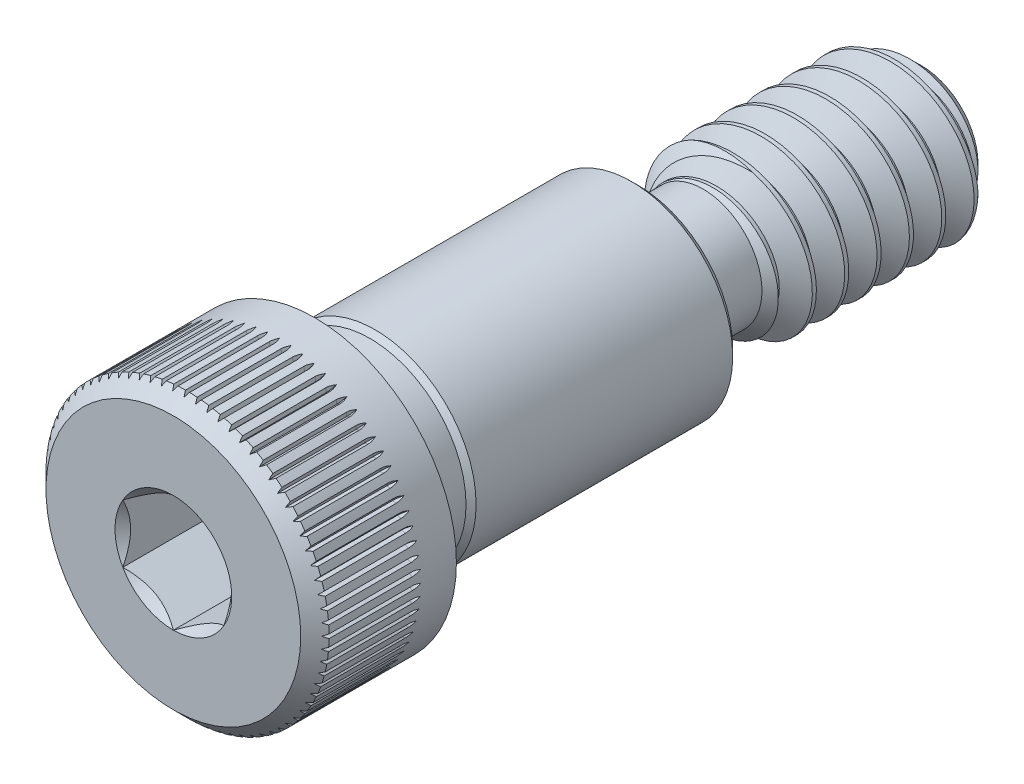
SolidWorks part; units mm, degrees
ref_plane "Front Plane" through (0, 0, 0) normal (0, 0, 1) x (1, 0, 0)
ref_plane "Top Plane" through (0, 0, 0) normal (0, 1, 0) x (1, 0, 0)
ref_plane "Right Plane" through (0, 0, 0) normal (1, 0, 0) x (0, 0, -1)
sketch "Sketch2" plane through (0, 0, 0) normal (1, 0, 0) x (0, 0, -1)
  line L0 (-14.6844, 0) -> (14.6844, 0) construction
  line L1 (-14.6844, 0) -> (-14.6844, 5.5562)
  line L2 (-14.6844, 5.5562) -> (-9.1281, 5.5563)
  line L3 (-9.1281, 5.5563) -> (-9.1281, 3.9688)
  line L4 (-9.1281, 3.9688) -> (3.5719, 3.9688)
  line L5 (3.5719, 3.175) -> (14.6844, 3.175)
  line L6 (14.6844, 3.175) -> (14.6844, 0)
  line L7 (14.605, 3.3125) -> (15.24, 2.2126) construction
  line L8 (15.24, 2.2126) -> (15.875, 3.3125) construction
  line L9 (15.875, 3.3125) -> (14.605, 3.3125) construction
  line L10 (14.6844, 3.175) -> (15.7956, 3.175) construction
  line L11 (15.24, 3.3125) -> (15.24, 3.175) construction
  line L12 (15.24, 3.175) -> (15.24, 2.3501) construction
  line L13 (15.24, 2.3501) -> (15.24, 2.2126) construction
  line L14 (15.1606, 2.3501) -> (15.3194, 2.3501)
  line L15 (14.6447, 3.2437) -> (15.8353, 3.2437)
  line L16 (15.3194, 2.3501) -> (15.8353, 3.2437)
  line L17 (15.1606, 2.3501) -> (14.6447, 3.2437)
  line L18 (14.6844, 0) -> (14.6844, -3.175) construction
  line L19 (3.5719, -3.9688) -> (3.5719, 0) construction
  line L20 (3.5719, 0) -> (3.5719, 3.9688) construction
  line L21 (-14.6844, 0) -> (-14.6844, -5.5562) construction
  point P11 (-6.7659, 3.9688)
  point P12 (11.5094, -3.175)
  point P22 (15.24, 3.2437)
  point P23 (3.0162, 0)
  point P25 (-3.0162, 0)
  point P26 (-9.1281, -5.5562)
  point P29 (3.5719, -3.9688)
  dimension "Head Height" = 5.5562
  dimension "Shoulder Diameter" = 7.9375
  dimension "Screw Size Decimal Equivalent" = 6.35
  dimension "Thread Length" = 11.1125
  dimension "Head Diameter" = 11.1125
  dimension "Undercut Length" = 2.3622
  dimension "Pitch" = 1.27
  dimension "D2" = 0.1588
  dimension "D1" = 3.175
  dimension "D3" = 11.6681
  dimension "D4" = 11.6681
  dimension "Shoulder Length" = 12.7
sketch "Sketch3" plane through (0, 0, 0) normal (0, 0, 1) x (1, 0, 0)
  line L1 (0, 2.2914) -> (-1.9844, 1.1457)
  line L2 (-1.9844, 1.1457) -> (-1.9844, -1.1457)
  line L3 (-1.9844, -1.1457) -> (0, -2.2914)
  line L4 (0, -2.2914) -> (1.9844, -1.1457)
  line L5 (1.9844, -1.1457) -> (1.9844, 1.1457)
  line L6 (1.9844, 1.1457) -> (0, 2.2914)
  circle A0 centre (0, 0) radius 1.9844 construction
  dimension "Drive Size" = 3.9688
sketch "Sketch4" plane through (0, 0, 0) normal (1, 0, 0) x (0, 0, -1)
  line L0 (-9.1281, 5.5563) -> (-14.1287, 5.5562)
  line L1 (-14.1287, 5.5562) -> (-14.6844, 5.0006)
  line L2 (-9.1281, 5.5563) -> (-9.1281, 3.9688)
  line L3 (-9.1281, 3.9688) -> (-8.9297, 3.7703)
  line L4 (-8.9297, 3.7703) -> (-6.9644, 3.7703)
  line L5 (-6.9644, 3.7703) -> (-6.7659, 3.9688)
  line L6 (-9.1281, 3.9688) -> (3.5719, 3.9688) construction
  line L7 (-14.6844, 0) -> (14.6844, 0) construction
  line L8 (-6.7659, 3.9688) -> (3.3073, 3.9688)
  line L9 (3.3073, 3.9688) -> (3.5719, 3.7042)
  line L10 (3.5719, 3.7042) -> (3.5719, 0)
  line L11 (3.5719, 3.9688) -> (3.5719, 3.7042) construction
  line L12 (3.5719, 3.7042) -> (3.5719, 3.4396) construction
  line L13 (3.5719, 3.4396) -> (3.5719, 3.175) construction
  line L14 (-14.6844, 5.0006) -> (-14.6844, 0)
  line L15 (-14.6844, 5.5562) -> (-9.1281, 5.5562) construction
  line L16 (-14.6844, 0) -> (3.5719, 0)
  dimension "D1" = 45
  dimension "D2" = 7.5406
  dimension "D3" = 45
  dimension "D4" = 45
  dimension "D5" = 10.0012
revolve "Revolve1" add sketch "Sketch4" angle 360 about L16
sketch "Sketch5" plane through (0, 0, 14.6844) normal (0, 0, 1) x (1, 0, 0)
  line L0 (1.9844, 1.1457) -> (0, 2.2914) construction
  line L1 (1.9844, -1.1457) -> (1.9844, 1.1457) construction
  line L2 (0, -2.2914) -> (1.9844, -1.1457) construction
  line L3 (-1.9844, -1.1457) -> (0, -2.2914) construction
  line L4 (-1.9844, 1.1457) -> (-1.9844, -1.1457) construction
  line L5 (0, 2.2914) -> (-1.9844, 1.1457) construction
  line L6 (1.9844, 1.1457) -> (0, 2.2914)
  line L7 (1.9844, -1.1457) -> (1.9844, 1.1457)
  line L8 (0, -2.2914) -> (1.9844, -1.1457)
  line L9 (-1.9844, -1.1457) -> (0, -2.2914)
  line L10 (-1.9844, 1.1457) -> (-1.9844, -1.1457)
  line L11 (0, 2.2914) -> (-1.9844, 1.1457)
extrude "Cut-Extrude1" cut sketch "Sketch5" against normal blind 4.1672
sketch "Sketch6" plane through (0, 0, 14.6844) normal (0, 0, 1) x (1, 0, 0)
  circle A0 centre (0, 0) radius 2.2914
extrude "Cut-Extrude4" cut sketch "Sketch6" against normal blind 4.1672 draft 45
sketch "Sketch7" plane through (0, 0, 0) normal (1, 0, 0) x (0, 0, -1)
  line L0 (3.5719, 3.175) -> (13.7319, 3.175)
  line L1 (3.5719, 3.175) -> (14.6844, 3.175) construction
  line L2 (13.7319, 3.175) -> (14.6844, 2.2225)
  line L3 (14.6844, 3.175) -> (14.6844, 0) construction
  line L4 (14.6844, 2.2225) -> (14.6844, 0)
  line L5 (14.6844, 0) -> (3.5719, 0)
  line L6 (3.5719, -3.7042) -> (3.5719, 3.7042) construction
  line L7 (3.5719, 0) -> (3.5719, 3.175)
  dimension "D1" = 45
  dimension "D2" = 0.9525
revolve "Revolve2" add sketch "Sketch7" angle 360 about L5
sketch "Sketch10" plane through (0, 0, 0) normal (1, 0, 0) x (0, 0, -1)
  line L0 (4.4355, 2.3114) -> (6.1119, 2.3114)
  line L1 (6.1119, 2.3114) -> (7.7692, 3.9688)
  line L2 (7.7692, 3.9688) -> (3.5719, 3.9688)
  line L3 (3.5719, 3.9688) -> (3.5719, 3.175)
  line L4 (3.5719, -3.7042) -> (3.5719, 3.7042) construction
  line L5 (14.6844, 0) -> (3.5719, 0) construction
  line L6 (-14.6844, 0) -> (14.6844, 0) construction
  arc A0 (3.5719, 3.175) -> (4.4355, 2.3114) centre (4.4355, 3.175) ccw
  dimension "Flat OD" = 4.6228
  dimension "Flat" = 2.54
  dimension "D3" = 45
revolve "Cut-Revolve1" cut sketch "Sketch10" angle 360 about L5
sketch "Sketch8" plane through (0, 0, -14.6844) normal (0, 0, -1) x (-1, 0, 0)
  circle A0 centre (0, 0) radius 3.175 construction
  circle A1 centre (0, 0) radius 3.175
curve "Helix/Spiral1" pitch 1.27 height 12.3825 radius 3.175 centre (0, 0, -14.6844) axis (0, 0, 1) start towards (0, 1, 0)
sketch "Sketch9" plane through (0, 0, 0) normal (1, 0, 0) x (0, 0, -1)
  line L0 (15.1606, 2.3501) -> (15.3194, 2.3501) construction
  line L1 (15.3194, 2.3501) -> (15.8353, 3.2437) construction
  line L2 (14.6447, 3.2437) -> (15.8353, 3.2437) construction
  line L3 (15.1606, 2.3501) -> (14.6447, 3.2437) construction
  line L4 (15.1606, 2.3501) -> (15.3194, 2.3501)
  line L5 (15.3194, 2.3501) -> (15.8353, 3.2437)
  line L6 (14.6447, 3.2437) -> (15.8353, 3.2437)
  line L7 (15.1606, 2.3501) -> (14.6447, 3.2437)
ref_plane "Plane1" through (0, 0, -6.1119) normal (0, 0, 1) x (1, 0, 0)
split "Split1" trim tools "Plane1" bodies to split 138 resulting bodies 139 140
sweep "Cut-Sweep1" cut profiles "Sketch9" path "Helix/Spiral1" align with end faces yes
combine bodies "Combine1" operation type add bodies to combine 141 139
sketch "Sketch11" plane through (0, 0, 14.6844) normal (0, 0, 1) x (1, 0, 0)
  line L0 (-0.0802, 5.5562) -> (0.0802, 5.5562)
  line L1 (0.0802, 5.5562) -> (0, 5.4173)
  line L2 (0, 0) -> (0, 5.5562) construction
  line L3 (0, 5.4173) -> (-0.0802, 5.5562)
  line L4 (0, 0) -> (5.5562, 0) construction
  circle A0 centre (0, 0) radius 5.5562 construction
  point P6 (0, 5.5562)
  dimension "D1" = 10.8347
  dimension "D2" = 60
  dimension "D3" = 0.1604
sketch "Sketch12" plane through (0, 0, 0) normal (1, 0, 0) x (0, 0, -1)
  line L0 (-14.6844, 5.4173) -> (-10.8525, 5.4173)
  line L1 (-10.3783, 5.8916) -> (-10.3783, 5.5562) construction
  line L2 (-14.6844, 5.5562) -> (-9.1281, 5.5562) construction
  arc A0 (-10.8525, 5.4173) -> (-10.3783, 5.8916) centre (-10.8525, 5.8916) ccw
  point P11 (-10.5172, 5.5563)
  dimension "D1" = 1.3891
sweep "Cut-Sweep2" cut profiles "Sketch11" path "Sketch12"
pattern_circular "CirPattern1" count 76 over 360 about axis through (0, 0, 14.6844) along (0, 0, -1) of "Cut-Sweep2"
equation "\"D2@Sketch2\" = \"Pitch@Sketch2\" / 8"
equation "\"D1@Sketch2\"=\"Pitch@Sketch2\"*2.5"
equation "\"D2@Sketch4\"=\"Shoulder Diameter@Sketch2\"*0.95"
equation "\"D5@Sketch4\"=\"Head Diameter@Sketch2\"*0.9"
equation "\"D1@Cut-Extrude1\"=\"Head Height@Sketch2\"*0.75"
equation "\"D1@Cut-Extrude4\"=\"D1@Cut-Extrude1\""
equation "\"D2@Sketch7\"=\"pitch@sketch2\"*0.75"
equation "\"D3@Helix/Spiral1\"=\"Thread Length@Sketch2\"+\"Pitch@Sketch2\""
equation "\"D4@Helix/Spiral1\"=\"Pitch@Sketch2\""
equation "\"D1@Sketch11\"=\"Head Diameter@Sketch2\"*0.975"
equation "\"D1@Sketch12\"=\"Head Height@Sketch2\"*0.25"
equation "\"D1@CirPattern1\"=\"Head Diameter@Sketch2\" * 3.14 / \"D3@Sketch11\" * 0.35"
equation "\"D3@Sketch2\"=\"Thread Length@Sketch2\"*1.05"
equation "\"D4@Sketch2\"=\"D3@Sketch2\""
